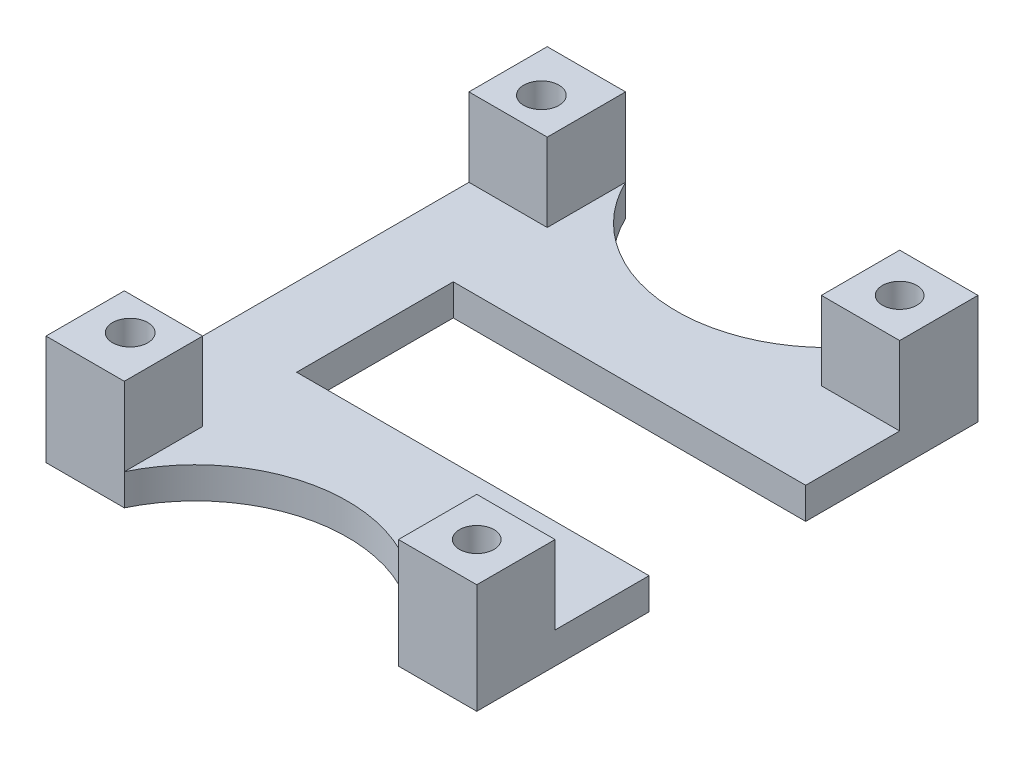
SolidWorks part; units mm, degrees
ref_plane "Front Plane" through (0, 0, 0) normal (0, 0, 1) x (1, 0, 0)
ref_plane "Top Plane" through (0, 0, 0) normal (0, 1, 0) x (1, 0, 0)
ref_plane "Right Plane" through (0, 0, 0) normal (1, 0, 0) x (0, 0, -1)
sketch "Sketch1" plane through (0, 0, 0) normal (0, 1, 0) x (1, 0, 0)
  line L0 (10, 10) -> (10, -10)
  line L1 (0, -20) -> (55, -20)
  line L2 (0, -20) -> (0, 20)
  line L3 (0, 20) -> (55, 20)
  line L4 (55, -20) -> (55, 20) construction
  line L5 (10, -10) -> (45, -10)
  line L6 (45, -10) -> (45, 10) construction
  line L7 (45, 10) -> (10, 10)
  line L8 (45, 10) -> (55, 10)
  line L11 (55, 10) -> (55, 20)
  line L13 (27.5, -20) -> (27.5, -10) construction
  line L14 (27.5, 10) -> (27.5, 20) construction
  line L16 (45, -10) -> (55, -10)
  line L17 (55, -20) -> (55, -10)
  line L18 (55, -20) -> (55, -32)
  line L19 (55, -32) -> (45, -32)
  line L20 (45, -32) -> (45, -20) construction
  line L21 (55, 20) -> (55, 32)
  line L22 (55, 32) -> (45, 32)
  line L23 (45, 32) -> (45, 20) construction
  line L24 (0, -20) -> (0, -32)
  line L25 (0, -32) -> (10, -32)
  line L26 (10, -32) -> (10, -20) construction
  line L27 (0, 20) -> (0, 32)
  line L28 (0, 32) -> (10, 32)
  line L29 (10, 32) -> (10, 20) construction
  line L30 (-7.7, 0) -> (7.7, 0) construction
  line L31 (0, 0) -> (55, 0) construction
  arc A26 (45, -32) -> (10, -32) centre (27.5, -40.4205) ccw
  arc A27 (10, 32) -> (45, 32) centre (27.5, 40.4205) ccw
  circle A46 centre (50, 27) radius 2.2
  circle A47 centre (50, -27) radius 2.2
  circle A49 centre (5, -26.25) radius 2.2479 construction
  circle A50 centre (5, -26.25) radius 2.2479
  circle A51 centre (5, 26.25) radius 2.2479 construction
  circle A52 centre (5, 26.25) radius 2.2479
  point P33 (27.5, 21)
  point P34 (27.5, -21)
  point P39 (0, 0)
  dimension "D18" = 4.4
  dimension "D19" = 4.4
  dimension "D1" = 40
  dimension "D2" = 55
  dimension "D3" = 10
  dimension "D22" = 10
  dimension "D23" = 10
  dimension "D24" = 10
  dimension "D13" = 5
  dimension "D16" = 5
  dimension "D7" = 10
  dimension "D10" = 12
  dimension "D11" = 12
  dimension "D12" = 10
  dimension "D9" = 5
  dimension "D14" = 5
  dimension "D15" = 12
  dimension "D17" = 10
  dimension "D20" = 10
  dimension "D21" = 12
  dimension "D27" = 1
  dimension "D28" = 1
extrude "Extrude-Body" add sketch "Sketch1" along normal blind 4 contours L1 L4 L3 L2 A47 A46 L7 L6 L5 L0 | L20 L19 L18 L1 A47 | L22 L23 L3 L21 A46 | L29 L28 L27 L3 | L25 L26 L1 L24 region at (9.3199, 0, 0) region at (27.5, 0, -20.5629) region at (54.4371, 0, 26)
sketch "Sketch5" plane through (0, 4, 0) normal (0, 1, 0) x (1, 0, 0)
  line L9 (45, -22) -> (55, -22)
  line L21 (55, -22) -> (55, -32)
  line L36 (55, -32) -> (45, -32)
  line L37 (45, -32) -> (45, -22)
  line L38 (55, 22) -> (55, 32)
  line L39 (55, 32) -> (45, 32)
  line L41 (45, 32) -> (45, 22)
  line L42 (45, 22) -> (55, 22)
  line L43 (10, 22) -> (10, 32)
  line L44 (10, 32) -> (0, 32)
  line L46 (0, 32) -> (0, 22)
  line L47 (0, -32) -> (0, 32) construction
  line L48 (0, 22) -> (10, 22)
  line L49 (10, -22) -> (0, -22)
  line L50 (0, -22) -> (0, -32)
  line L51 (0, -32) -> (10, -32)
  line L52 (10, -32) -> (10, -22)
  circle A0 centre (50, 27) radius 2.2
  circle A3 centre (50, -27) radius 2.2
  circle A11 centre (50, 27) radius 2.2 construction
  circle A12 centre (50, -27) radius 2.2 construction
  circle A13 centre (5, 26.25) radius 2.2479 construction
  circle A14 centre (5, 26.25) radius 2.2479
  circle A15 centre (5, -26.25) radius 2.2479 construction
  circle A16 centre (5, -26.25) radius 2.2479
  dimension "D1" = 10
  dimension "D2" = 10
  dimension "D3" = 10
  dimension "D4" = 10
  dimension "D5" = 10
  dimension "D6" = 10
  dimension "D7" = 10
  dimension "D8" = 10
extrude "Extrude-Legs" add sketch "Sketch5" along normal blind 10
sketch "Sketch6" plane through (0, 0, 0) normal (0, -1, 0) x (1, 0, 0)
  circle A3 centre (50, 27) radius 4.215
  circle A5 centre (50, -27) radius 4.215
  dimension "D1" = 8.43
  dimension "D3" = 8.43
extrude "Cut-Bolt Head Insets" cut sketch "Sketch6" against normal blind 2.5
equation "\"boltdiameter\"=4.4"
equation "\"D18@Sketch1\"=\"boltdiameter\""
equation "\"D19@Sketch1\"=\"boltdiameter\""
equation "\"boltfacediameter\"=7"
equation "\"insetNutFlat\"=8.4"
equation "\"screwInset\"=8.43"
equation "\"D1@Sketch6\"=\"screwInset\""
equation "\"D3@Sketch6\"=\"screwInset\""
equation "\"slotLength\"=80"
